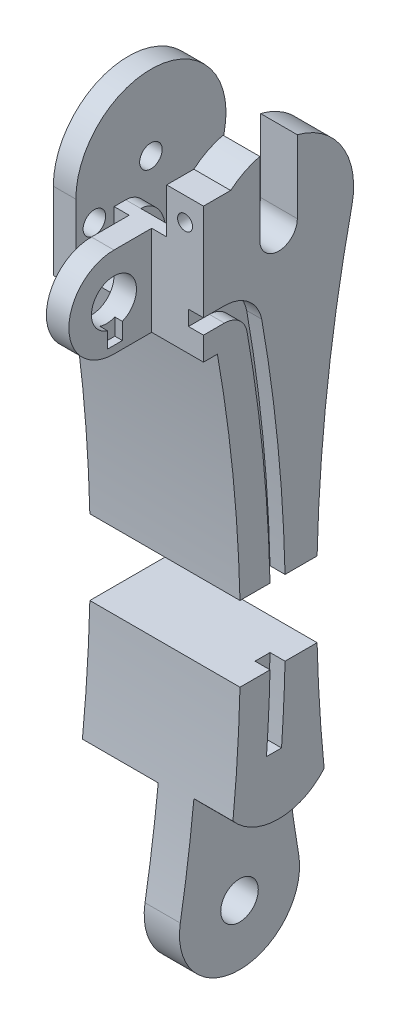
SolidWorks part; units mm, degrees
ref_plane "Front Plane" through (0, 0, 0) normal (0, 0, 1) x (1, 0, 0)
ref_plane "Top Plane" through (0, 0, 0) normal (0, 1, 0) x (1, 0, 0)
ref_plane "Right Plane" through (0, 0, 0) normal (1, 0, 0) x (0, 0, -1)
sketch "Sketch1" plane through (0, 0, 0) normal (1, 0, 0) x (0, 0, -1)
  arc A0 (9.7654, 20.1165) -> (-9.7654, 20.1165) centre (0, 22.2701) ccw
  arc A1 (-7.8874, -56.3924) -> (7.8874, -56.3924) centre (0, -57.7299) ccw
  arc A2 (-7.8874, -56.3924) -> (-9.7654, 20.1165) centre (-205.0724, -22.9549) ccw
  circle A3 centre (0, 22.2701) radius 1.5
  arc A4 (9.7654, 20.1165) -> (7.8874, -56.3924) centre (205.0724, -22.9549) ccw
  circle A5 centre (0, -57.7299) radius 2.5
extrude "Boss-Extrude1" add sketch "Sketch1" along normal blind 20
sketch "Sketch2" plane through (0, 0, 0) normal (0, 0, 1) x (1, 0, 0)
  line L1 (0, -65.7299) -> (8.1, -65.7299)
  line L2 (0, -65.7299) -> (0, -45.7299)
  line L3 (0, -45.7299) -> (8.1, -45.7299)
  line L4 (8.1, -65.7299) -> (8.1, -45.7299)
  line L5 (20, -65.7299) -> (14.8, -65.7299)
  line L6 (20, -65.7299) -> (20, -45.7299)
  line L7 (20, -45.7299) -> (14.8, -45.7299)
  line L8 (14.8, -65.7299) -> (14.8, -45.7299)
  line L11 (3, 32.2701) -> (8.1, 32.2701)
  line L12 (3, 32.2701) -> (3, 12.2701)
  line L13 (3, 12.2701) -> (8.1, 12.2701)
  line L14 (8.1, 32.2701) -> (8.1, 12.2701)
extrude "Cut-Extrude1" cut sketch "Sketch2" against normal blind 20 and the other way blind 20
sketch "Sketch3" plane through (8.1, 0, 0) normal (-1, 0, 0) x (0, 0, 1)
  line L0 (8.5, 22.2701) -> (8.5, 40.9095)
  line L1 (8.5, 40.9095) -> (-17.5287, 40.9095)
  line L2 (-17.5287, 40.9095) -> (-17.5287, 13.7701)
  line L3 (0, 13.7701) -> (-17.5287, 13.7701)
  arc A0 (0, 13.7701) -> (8.5, 22.2701) centre (0, 22.2701) ccw
extrude "Cut-Extrude2" cut sketch "Sketch3" against normal blind 9
sketch "Sketch4" plane through (8.1, 0, 0) normal (-1, 0, 0) x (0, 0, 1)
  line L0 (8.5, 27.5379) -> (8.2838, 12.7416)
  line L1 (8.2838, 12.7416) -> (10.2838, 12.7416)
  line L2 (10.2838, 12.7416) -> (10.2838, 27.5379)
  line L3 (10.2838, 27.5379) -> (8.5, 27.5379)
  arc A0 (9.7654, 20.1165) -> (6.3734, -45.7299) centre (205.0724, -22.9549) ccw construction
extrude "Boss-Extrude2" add sketch "Sketch4" against normal through all
sketch "Sketch5" plane through (8.1, 0, 0) normal (-1, 0, 0) x (0, 0, 1)
  line L4 (8.1452, 11.9686) -> (8.4478, 23.9686)
  line L6 (15.0224, 23.9686) -> (9.8547, 23.9686)
  line L8 (8.1452, 11.9686) -> (15.0224, 11.9686)
  line L9 (8.5, 27.5379) -> (8.4045, 20.9993) construction
  line L10 (8.4478, 23.9686) -> (9.8547, 23.9686)
  circle A2 centre (15.0224, 17.9686) radius 3
  arc A5 (15.0224, 11.9686) -> (15.0224, 23.9686) centre (15.0224, 17.9686) ccw
  arc A6 (9.7654, 20.1165) -> (-9.7654, 20.1165) centre (0, 22.2701) ccw construction
  arc A7 (9.7654, 20.1165) -> (6.3734, -45.7299) centre (205.0724, -22.9549) ccw construction
extrude "Boss-Extrude3" add sketch "Sketch5" against normal blind 5
sketch "Sketch12" plane through (13.1, 0, 0) normal (1, 0, 0) x (0, 0, -1)
  line L2 (-13.9029, 14.9686) -> (-13.9029, 12.9686)
  line L4 (-15.9029, 14.9686) -> (-15.9029, 15.2943)
  line L5 (-15.9029, 15.2943) -> (-13.9029, 15.2943)
  line L6 (-13.9029, 12.9686) -> (-15.9029, 12.9686)
  line L7 (-13.9029, 14.9686) -> (-13.9029, 15.2943)
  line L11 (-15.9029, 14.9686) -> (-15.9029, 12.9686)
extrude "Cut-Extrude6" cut sketch "Sketch12" against normal blind 1
sketch "Sketch13" plane through (17.1, 0, 0) normal (-1, 0, 0) x (0, 0, 1)
  circle A0 centre (0, 22.2701) radius 2.5
extrude "Cut-Extrude7" cut sketch "Sketch13" against normal blind 4
sketch "Sketch15" plane through (0, 0, 0) normal (-1, 0, 0) x (0, 0, 1)
  line L0 (10, 22.2701) -> (10, 11.9686)
  line L1 (8.1452, 11.9686) -> (15.0224, 11.9686) construction
  line L2 (10, 11.9686) -> (8.1452, 11.9686)
  line L3 (10, 22.2701) -> (7.5957, 11.9686)
  line L4 (7.5957, 11.9686) -> (8.1452, 11.9686)
  arc A0 (9.7654, 20.1165) -> (-9.7654, 20.1165) centre (0, 22.2701) ccw construction
extrude "Boss-Extrude4" add sketch "Sketch15" against normal blind 3
sketch "Sketch16" plane through (20, 0, 0) normal (1, 0, 0) x (0, 0, -1)
  line L0 (-10.2838, 23.9686) -> (-9.8547, 23.9686)
  line L1 (-10.2838, 23.9686) -> (-10.2838, 27.5379)
  line L2 (-10.2838, 27.5379) -> (-8.5, 27.5379) construction
  line L3 (-10.2838, 12.7416) -> (-10.2838, 27.5379) construction
  line L4 (-10.2838, 27.5379) -> (-8.5, 27.5379)
  arc A0 (-8.5, 27.5379) -> (-9.8547, 23.9686) centre (0, 22.2701) ccw
extrude "Cut-Extrude9" cut sketch "Sketch16" against normal blind 3
sketch "Sketch17" plane through (0, 0, 10.2838) normal (0, 0, 1) x (1, 0, 0)
  line L1 (17.1, 27.5379) -> (8.1, 27.5379)
  line L2 (17.1, 27.5379) -> (17.1, 23.9686)
  line L3 (17.1, 23.9686) -> (8.1, 23.9686)
  line L4 (8.1, 27.5379) -> (8.1, 23.9686)
extrude "Cut-Extrude11" cut sketch "Sketch17" against normal blind 3
sketch "Sketch18" plane through (13.1, 0, 0) normal (1, 0, 0) x (0, 0, -1)
  line L1 (-10.2838, 12.7416) -> (-4.5128, 12.7416)
  line L2 (-10.2838, 12.7416) -> (-10.2838, 11.9686)
  line L3 (-10.2838, 11.9686) -> (-4.5128, 11.9686)
  line L4 (-4.5128, 12.7416) -> (-4.5128, 11.9686)
extrude "Boss-Extrude5" add sketch "Sketch18" along normal through all and the other way blind 1
sketch "Sketch19" plane through (0, 12.2701, 0) normal (0, 1, 0) x (1, 0, 0)
  line L1 (8.1, -8.1989) -> (3, -8.1989)
  line L2 (8.1, -8.1989) -> (8.1, 8.1989)
  line L3 (8.1, 8.1989) -> (3, 8.1989)
  line L4 (3, -8.1989) -> (3, 8.1989)
extrude "Cut-Extrude12" cut sketch "Sketch19" against normal up to surface (0.3015 mm away) up to face at (1.5, 11.9686, 9.0726)
sketch "Sketch20" plane through (17.1, 0, 0) normal (-1, 0, 0) x (0, 0, 1)
  line L1 (2.5, 22.2701) -> (-2.5, 22.2701)
  line L2 (2.5, 22.2701) -> (2.5, 34.6894)
  line L3 (2.5, 34.6894) -> (-2.5, 34.6894)
  line L4 (-2.5, 22.2701) -> (-2.5, 34.6894)
  circle A0 centre (0, 22.2701) radius 2.5 construction
extrude "Cut-Extrude13" cut sketch "Sketch20" against normal blind 10
sketch "Sketch21" plane through (17.1, 0, 0) normal (-1, 0, 0) x (0, 0, 1)
  line L1 (-8.4732, 13.7701) -> (0.2785, 12.274)
  line L3 (2.5, 22.2701) -> (2.5, 31.9526)
  line L5 (-2.5, 22.2701) -> (-2.5, 31.9526)
  arc A0 (0.2785, 12.274) -> (2.5, 31.9526) centre (0, 22.2701) ccw
  arc A1 (-2.5, 22.2701) -> (2.5, 22.2701) centre (0, 22.2701) ccw
  arc A2 (-2.5, 31.9526) -> (-9.7654, 20.1165) centre (0, 22.2701) ccw
  arc A7 (-8.4732, 13.7701) -> (-9.7654, 20.1165) centre (-205.0724, -22.9549) ccw
extrude "Boss-Extrude6" add sketch "Sketch21" along normal blind 2
sketch "Sketch23" plane through (0, 0, 10.2838) normal (0, 0, 1) x (1, 0, 0)
  line L1 (15.1, 23.9686) -> (20, 23.9686)
  line L2 (15.1, 23.9686) -> (15.1, 29.9686)
  line L3 (15.1, 29.9686) -> (20, 29.9686)
  line L4 (20, 23.9686) -> (20, 29.9686)
extrude "Boss-Extrude7" add sketch "Sketch23" against normal blind 4
sketch "Sketch22" plane through (0, 0, 10.2838) normal (0, 0, 1) x (1, 0, 0)
  circle A1 centre (17.55, 26.8701) radius 1
extrude "Cut-Extrude15" cut sketch "Sketch22" against normal blind 8
sketch "Sketch24" plane through (8.1, 0, 0) normal (-1, 0, 0) x (0, 0, 1)
  line L0 (5.1478, 19.7374) -> (5.1478, 15.5063)
  line L2 (8.4478, 23.9686) -> (8.4478, 15.5063)
  line L3 (8.4478, 15.5063) -> (5.1478, 15.5063)
  arc A0 (0, 13.7701) -> (8.3673, 20.7738) centre (0, 22.2701) ccw construction
  ellipse E0 centre (8.4478, 19.7374) end of major axis (8.4478, 15.5063) minor radius 3.3 (8.4478, 23.9686) -> (5.1478, 19.7374) ccw
extrude "Boss-Extrude8" add sketch "Sketch24" against normal blind 2
sketch "Sketch14" plane through (0, 0, 0) normal (-1, 0, 0) x (0, 0, 1)
  circle A3 centre (7.5326, 18.3318) radius 1.5
extrude "Cut-Extrude8" cut sketch "Sketch14" against normal up to surface (10.1 mm away) up to face at (10.1, 20.14, 6.7306)
sketch "Sketch25" plane through (8.1, 0, 0) normal (-1, 0, 0) x (0, 0, 1)
  line L0 (12, -45.7299) -> (8.3462, -36.9607)
  line L1 (-12, -45.7299) -> (-12, -57.7299)
  line L2 (12, -45.7299) -> (12, -57.7299)
  line L3 (-12, -45.7299) -> (-8.3462, -36.9607)
  line L5 (2.5, -53.2274) -> (2.5, -45.7299)
  line L7 (-2.5, -53.2274) -> (-2.5, -45.7299)
  arc A0 (-2.5, -53.2274) -> (2.5, -53.2274) centre (0, -57.7299) ccw
  arc A1 (-12, -57.7299) -> (12, -57.7299) centre (0, -57.7299) ccw
  arc A2 (2.5, -45.7299) -> (8.3462, -36.9607) centre (0, -37.7299) ccw
  arc A4 (-8.3462, -36.9607) -> (-2.5, -45.7299) centre (0, -37.7299) ccw
extrude "Cut-Extrude17" cut sketch "Sketch25" against normal blind 2 and the other way up to surface (8.1 mm away) other way up to face at (0, 18.3318, 9.0326)
sketch "Sketch26" plane through (20, 0, 0) normal (1, 0, 0) x (0, 0, -1)
  line L0 (-10.2838, 11.9686) -> (-10.2838, 29.9686) construction
  line L1 (-7.21, 15.0854) -> (-10.2838, 15.0854)
  line L3 (-7.21, 17.0854) -> (-10.2838, 17.0854)
  line L4 (-10.2838, 15.0854) -> (-10.2838, 17.0854)
  line L8 (-1.6082, -37.73) -> (0.397, -37.73)
  arc A0 (-4.2066, 12.6671) -> (-7.21, 15.0854) centre (-7.21, 12.0113) ccw
  arc A1 (-2.2434, 13.0504) -> (-7.21, 17.0854) centre (-7.21, 12.0113) ccw
  arc A2 (-2.3994, -46.1854) -> (-4.2066, 12.6671) centre (-205.0724, -22.9549) ccw
  arc A3 (-1.6082, -37.73) -> (-4.2066, 12.6671) centre (-205.0724, -22.9549) ccw
  circle A4 centre (-7.21, 12.0113) radius 5.0741 construction
  circle A5 centre (-7.21, 12.0113) radius 3.0741 construction
  arc A6 (-0.4124, -46.4131) -> (-2.2373, 13.0163) centre (-205.0724, -22.9549) ccw
  arc A7 (0.397, -37.73) -> (-2.2434, 13.0504) centre (-205.0724, -22.9549) ccw
  dimension "D3" = 2
  dimension "D1" = 4
  dimension "D2" = 6
extrude "Cut-Extrude18" cut sketch "Sketch26" against normal blind 2
sketch "Sketch29" plane through (20, 0, 0) normal (1, 0, 0) x (0, 0, -1)
  line L1 (8, -37.7299) -> (8.1403, -37.7299)
  line L2 (-15.7549, -37.7299) -> (-8, -37.7299)
  line L3 (-15.7549, -37.7299) -> (-15.7549, -45.9375)
  line L4 (-15.7549, -45.9375) -> (8.1403, -45.9375)
  line L5 (8.1403, -37.7299) -> (8.1403, -45.9375)
  arc A0 (-8, -37.7299) -> (8, -37.7299) centre (0, -37.7299) ccw
extrude "Cut-Extrude20" cut sketch "Sketch29" against normal up to surface (5.2 mm away) up to face at (14.8, -57.7299, -2.5)
sketch "Sketch30" plane through (0, 0, 10.2838) normal (0, 0, 1) x (1, 0, 0)
  line L1 (13.1, 11.9686) -> (20, 11.9686)
  line L2 (13.1, 11.9686) -> (13.1, 31.9686)
  line L3 (13.1, 31.9686) -> (20, 31.9686)
  line L4 (20, 11.9686) -> (20, 31.9686)
extrude "Cut-Extrude21" cut sketch "Sketch30" against normal up to surface (0.2838 mm away) up to face at (1.5, 17.1194, 10)
sketch "Sketch31" plane through (0, 23.9686, 0) normal (0, 1, 0) x (1, 0, 0)
  line L0 (8.1, -15.0224) -> (8.1, -8.4478) construction
  line L1 (8.1, -10) -> (10.1, -10)
  line L2 (8.1, -10) -> (8.1, -21.0224)
  line L3 (8.1, -21.0224) -> (10.1, -21.0224)
  line L4 (10.1, -10) -> (10.1, -21.0224)
  line L5 (8.1, -21.0224) -> (13.1, -21.0224) construction
extrude "Cut-Extrude22" cut sketch "Sketch31" against normal up to next
sketch "Sketch32" plane through (8.1, 0, 0) normal (-1, 0, 0) x (0, 0, 1)
  line L0 (-8.4732, 13.7701) -> (-8.4732, 5.4011)
  line L2 (5.1478, 15.5063) -> (-8.4732, 5.4011)
  line L5 (5.1478, 15.5063) -> (-8.4732, 13.7701)
extrude "Cut-Extrude23" cut sketch "Sketch32" against normal blind 7
sketch "Sketch33" plane through (20, 0, 0) normal (1, 0, 0) x (0, 0, -1)
  line L2 (-9.3048, -22.9549) -> (-9.3048, -27.9549)
  line L3 (-9.3048, -27.9549) -> (8.8924, -27.9549)
  line L4 (8.8924, -22.9549) -> (8.8924, -27.9549)
  line L6 (-9.3048, -22.9549) -> (-9.3048, -17.9549)
  line L7 (-9.3048, -17.9549) -> (8.8924, -17.9549)
  line L8 (8.8924, -22.9549) -> (8.8924, -17.9549)
extrude "Cut-Extrude24" cut sketch "Sketch33" against normal through all
